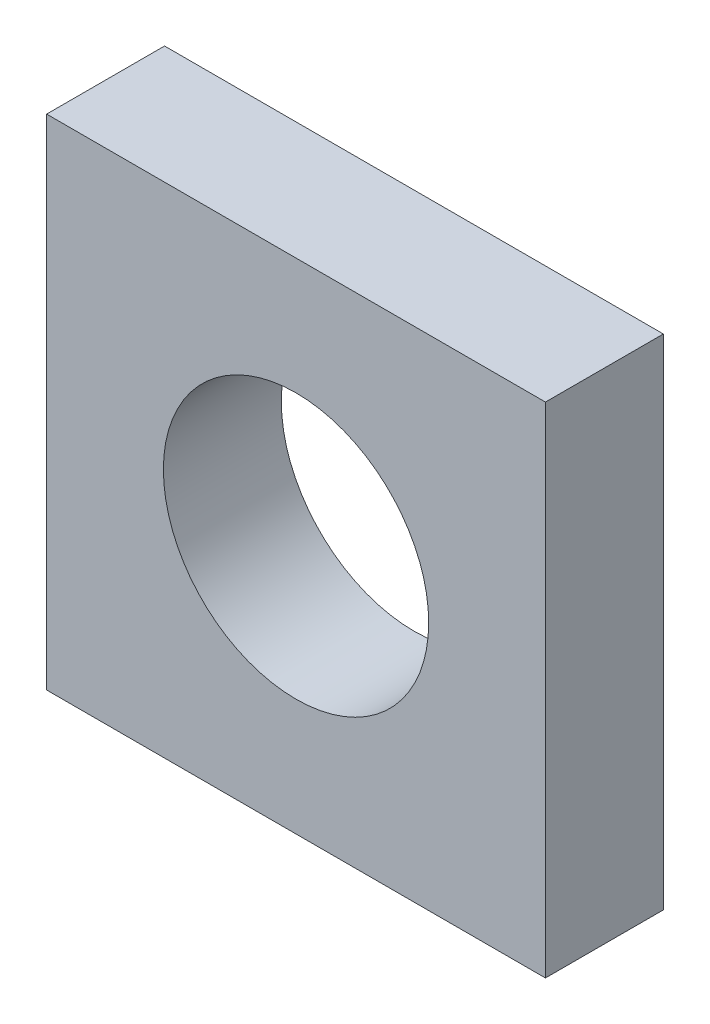
SolidWorks part; units mm, degrees
ref_plane "Front Plane" through (0, 0, 0) normal (0, 0, 1) x (1, 0, 0)
ref_plane "Top Plane" through (0, 0, 0) normal (0, 1, 0) x (1, 0, 0)
ref_plane "Right Plane" through (0, 0, 0) normal (1, 0, 0) x (0, 0, -1)
sketch "Sketch1" plane through (0, 0, 0) normal (0, 0, 1) x (1, 0, 0)
  line L1 (-21.15, -21.15) -> (21.15, -21.15)
  line L2 (-21.15, -21.15) -> (-21.15, 21.15)
  line L3 (-21.15, 21.15) -> (21.15, 21.15)
  line L4 (21.15, -21.15) -> (21.15, 21.15)
  line L5 (-21.15, -21.15) -> (21.15, 21.15) construction
  line L6 (-21.15, 21.15) -> (21.15, -21.15) construction
  circle A0 centre (0, 0) radius 11.25
  point P0 (0, 0)
  dimension "D3" = 22.5
  dimension "D1" = 21.15
extrude "Boss-Extrude1" add sketch "Sketch1" along normal blind 10
